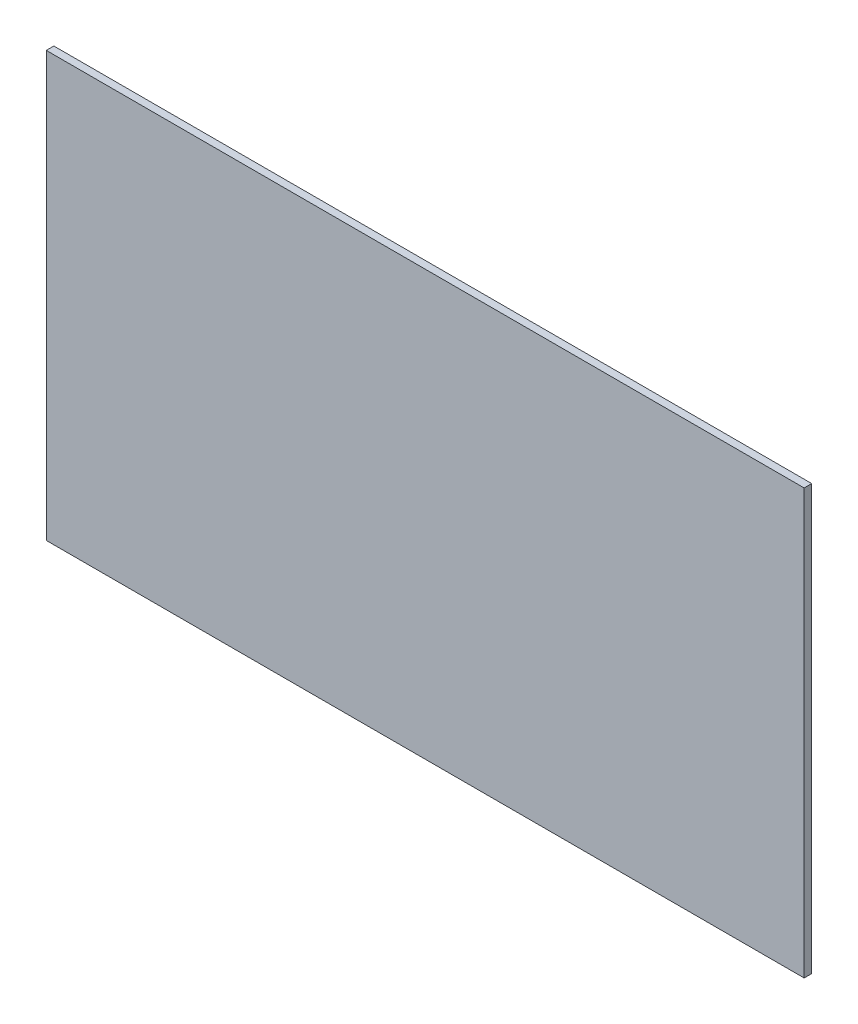
SolidWorks part; units mm, degrees
ref_plane "Front Plane" through (0, 0, 0) normal (0, 0, 1) x (1, 0, 0)
ref_plane "Top Plane" through (0, 0, 0) normal (0, 1, 0) x (1, 0, 0)
ref_plane "Right Plane" through (0, 0, 0) normal (1, 0, 0) x (0, 0, -1)
sketch "Sketch1" plane through (0, 0, 0) normal (0, 0, 1) x (1, 0, 0)
  line L1 (0, 0) -> (317.5, 0)
  line L2 (0, 0) -> (0, 177.8)
  line L3 (0, 177.8) -> (317.5, 177.8)
  line L4 (317.5, 0) -> (317.5, 177.8)
  dimension "D1" = 177.8
  dimension "D2" = 317.5
extrude "Boss-Extrude1" add sketch "Sketch1" along normal blind 3.175
